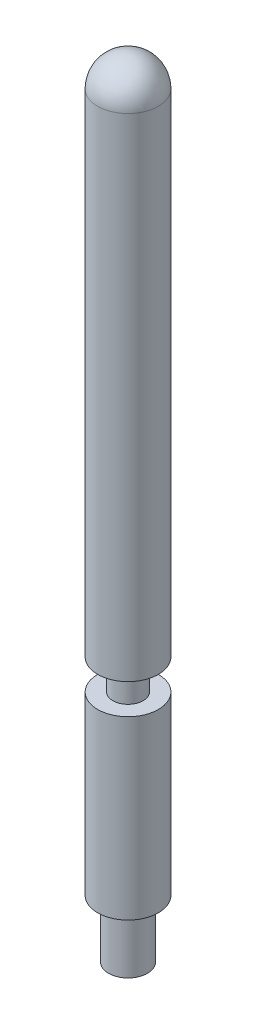
SolidWorks part; units mm, degrees
material "CA"
ref_plane "Front Plane" through (0, 0, 0) normal (0, 0, 1) x (1, 0, 0)
ref_plane "Top Plane" through (0, 0, 0) normal (0, 1, 0) x (1, 0, 0)
ref_plane "Right Plane" through (0, 0, 0) normal (1, 0, 0) x (0, 0, -1)
sketch "Sketch1" plane through (0, 0, 0) normal (0, 1, 0) x (1, 0, 0)
  circle A0 centre (0, 0) radius 5
  dimension "D1" = 10
extrude "Boss-Extrude1" add sketch "Sketch1" along normal blind 29
sketch "Sketch2" plane through (0, 29, 0) normal (0, 1, 0) x (1, 0, 0)
  circle A0 centre (0, 0) radius 2.5
  dimension "D1" = 5
extrude "Boss-Extrude2" add sketch "Sketch2" along normal blind 5
sketch "Sketch3" plane through (0, 0, 0) normal (1, 0, 0) x (0, 0, -1)
  line L0 (0, 0) -> (0, 34) construction
  line L1 (2.5, 34) -> (-2.5, 34) construction
  line L2 (0, 34) -> (0, 120)
  line L3 (0, 34) -> (5, 34)
  line L4 (5, 34) -> (5, 115)
  line L5 (0, 120) -> (-4.0683, 120) construction
  arc A0 (5, 115) -> (0, 120) centre (0, 115) ccw
  dimension "D1" = 90
  dimension "D2" = 5
  dimension "D3" = 86
ref_axis "Axis1" through (0, 34, 0) along (0, 1, 0)
revolve "Revolve1" add sketch "Sketch3" angle 360 about axis through (0, 34, 0) along (0, 1, 0)
sketch "Sketch4" plane through (0, 0, 0) normal (0, -1, 0) x (1, 0, 0)
  circle A0 centre (0, 0) radius 3.2
  dimension "D1" = 6.4
extrude "Boss-Extrude3" add sketch "Sketch4" along normal blind 9.525
